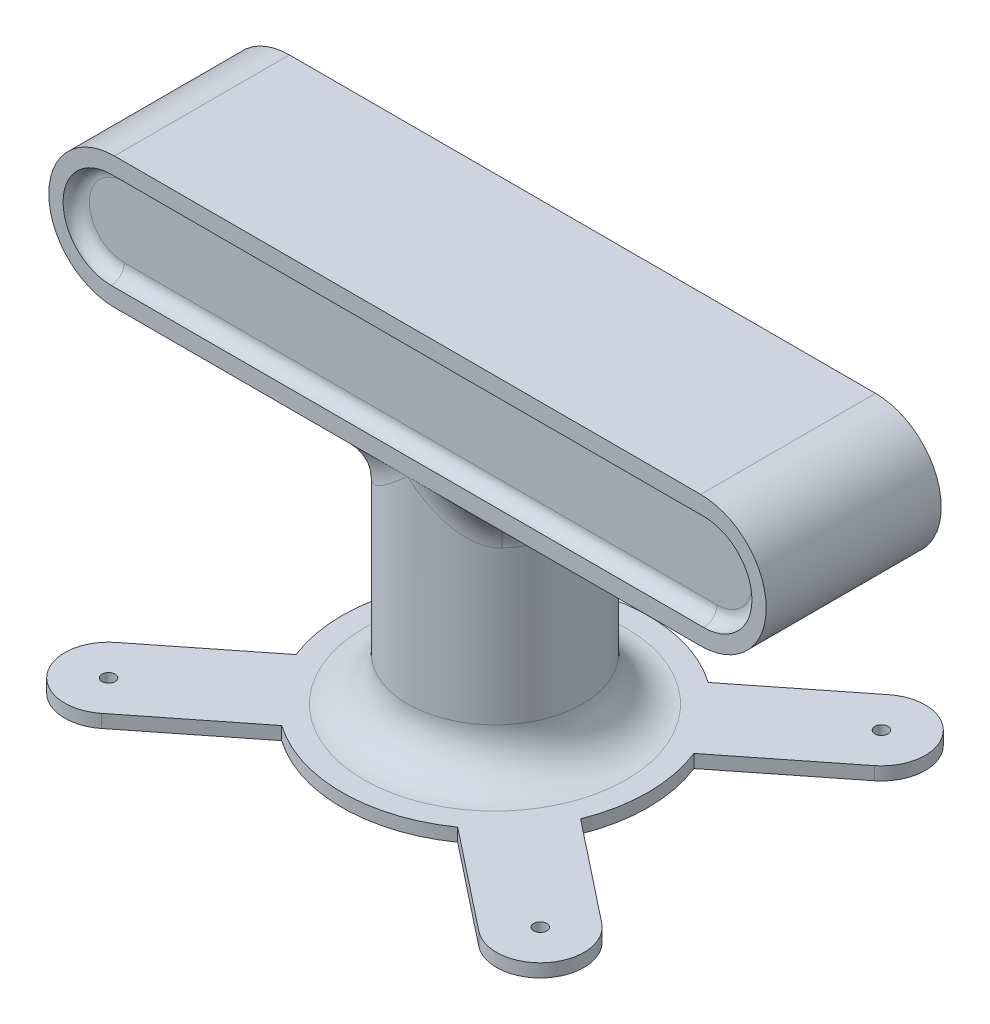
SolidWorks part; units mm, degrees
ref_plane "前视基准面" through (0, 0, 0) normal (0, 0, 1) x (1, 0, 0)
ref_plane "上视基准面" through (0, 0, 0) normal (0, 1, 0) x (1, 0, 0)
ref_plane "右视基准面" through (0, 0, 0) normal (1, 0, 0) x (0, 0, -1)
sketch "草图1" plane through (0, 0, 0) normal (0, 0, 1) x (1, 0, 0)
  line L0 (-67, 0) -> (67, 0) construction
  line L1 (-67, 15) -> (67, 15)
  line L2 (-67, -15) -> (67, -15)
  arc A0 (-67, 15) -> (-67, -15) centre (-67, 0) ccw
  arc A1 (67, -15) -> (67, 15) centre (67, 0) ccw
  point P3 (0, 0)
  dimension "D2" = 15
  dimension "D1" = 134
  dimension "D3" = 0
extrude "凸台-拉伸1" add sketch "草图1" along normal blind 40
sketch "草图2" plane through (0, -15, 0) normal (0, -1, 0) x (1, 0, 0)
  line L0 (0, 40) -> (0, 0) construction
  line L1 (-67, 40) -> (67, 40) construction
  circle A0 centre (0, 20) radius 20
  dimension "D1" = 40
extrude "凸台-拉伸2" add sketch "草图2" along normal blind 55
fillet "圆角1" radius 10 2 edges at (-20, -15, 20) (20, -15, 20)
sketch "草图3" plane through (0, -70, 0) normal (0, -1, 0) x (1, 0, 0)
  line L0 (0, 91.5944) -> (0, -67.0919) construction
  line L1 (49.35, 59) -> (-49.35, -19) construction
  line L2 (49.35, 59) -> (-49.35, 59) construction
  line L3 (49.35, 59) -> (49.35, -19) construction
  line L4 (49.35, -19) -> (-49.35, -19) construction
  line L5 (-49.35, 59) -> (-49.35, -19) construction
  line L6 (55.5503, 51.1542) -> (-43.1497, -26.8458)
  line L7 (43.1497, 66.8458) -> (-55.5503, -11.1542)
  line L8 (49.35, -19) -> (-49.35, 59) construction
  line L9 (43.1497, -26.8458) -> (-55.5503, 51.1542)
  line L10 (55.5503, -11.1542) -> (-43.1497, 66.8458)
  circle A0 centre (49.35, 59) radius 1.5
  circle A1 centre (-49.35, 59) radius 1.5
  circle A2 centre (-49.35, -19) radius 1.5
  circle A3 centre (49.35, -19) radius 1.5
  arc A4 (55.5503, 51.1542) -> (43.1497, 66.8458) centre (49.35, 59) ccw
  arc A5 (-55.5503, -11.1542) -> (-43.1497, -26.8458) centre (-49.35, -19) ccw
  arc A6 (43.1497, -26.8458) -> (55.5503, -11.1542) centre (49.35, -19) ccw
  arc A7 (-43.1497, 66.8458) -> (-55.5503, 51.1542) centre (-49.35, 59) ccw
  circle A8 centre (0, 20) radius 35
  point P11 (0, 20)
  point P16 (0, 20)
  circle M6 centre (0, 20) radius 20
  dimension "D5" = 3
  dimension "D6" = 3
  dimension "D7" = 3
  dimension "D8" = 3
  dimension "D9" = 10
  dimension "D10" = 10
  dimension "D11" = 70
  dimension "D1" = 78
  dimension "D2" = 59
  dimension "D3" = 98.7
  dimension "D4" = 49.35
extrude "凸台-拉伸3" add sketch "草图3" along normal blind 3 contours A8 L6 A4 L7 A0 | L6 A8 L7 M6 | L10 A8 L6 M6 | L9 A8 L10 M6 | A8 L9 A6 L10 A3 | L6 A8 L9 M6 | L7 A8 L6 M6 | L7 A8 L10 M6 | A8 L10 A7 L9 A1 | L10 A8 L9 M6 | L7 L10 L9 M6 | L6 L10 L7 L9 | L10 L6 L7 M6 | L10 L7 M6 | L10 L6 L9 M6 | L10 L6 M6 | L9 L6 M6 | L6 L9 L7 M6 | L7 L9 M6 | L9 A8 L7 M6 | A8 L7 A5 L6 A2
fillet "圆角2" radius 10 1 edges at (20, -70, 20)
sketch "草图5" plane through (0, 0, 40) normal (0, 0, 1) x (1, 0, 0)
  line L0 (-67.7395, 0) -> (67.7395, 0) construction
  line L1 (-67.7395, 11) -> (67.7395, 11)
  line L2 (-67.7395, -11) -> (67.7395, -11)
  arc A0 (-67.7395, 11) -> (-67.7395, -11) centre (-67.7395, 0) ccw
  arc A1 (67.7395, -11) -> (67.7395, 11) centre (67.7395, 0) ccw
  point P4 (0, 0)
  dimension "D3" = 11
  dimension "D1" = 135.479
  dimension "D2" = 0
extrude "切除-拉伸1" cut sketch "草图5" against normal blind 3
fillet "圆角3" radius 3 4 edges at (0, -11, 37) (-78.7395, 0, 37) (0, 11, 37) (78.7395, 0, 37)
